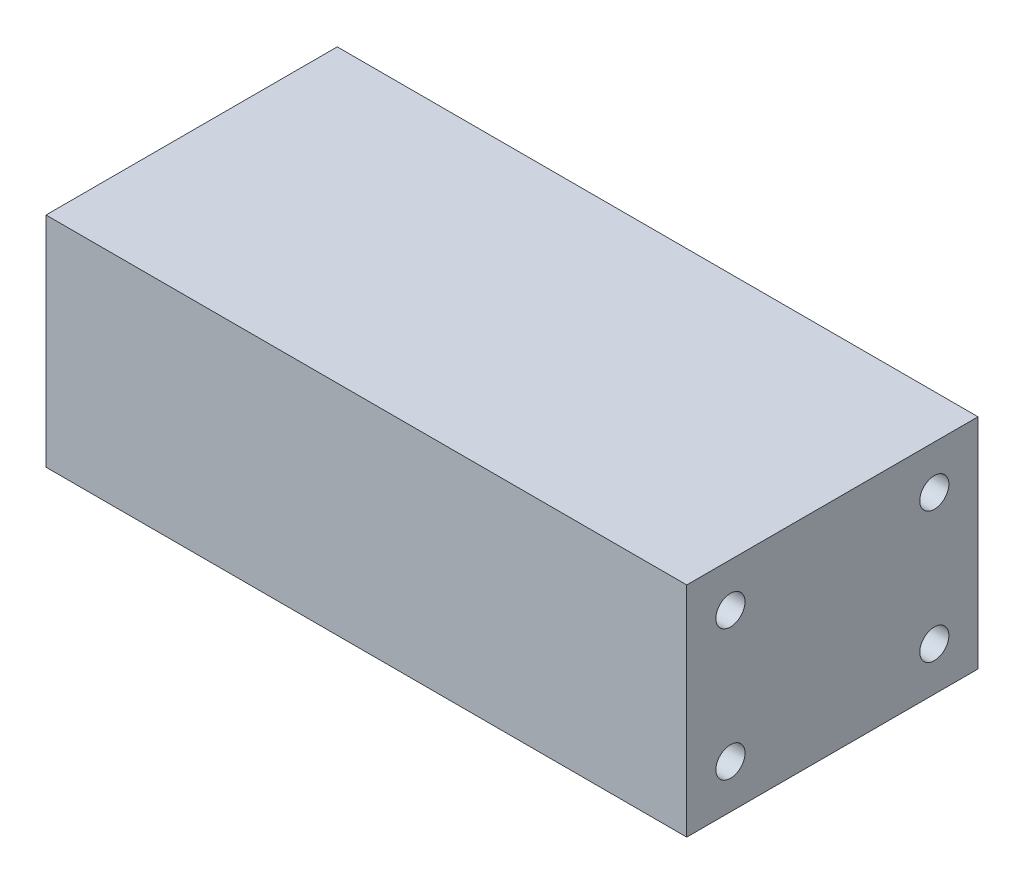
SolidWorks part; units mm, degrees
ref_plane "Front Plane" through (0, 0, 0) normal (0, 0, 1) x (1, 0, 0)
ref_plane "Top Plane" through (0, 0, 0) normal (0, 1, 0) x (1, 0, 0)
ref_plane "Right Plane" through (0, 0, 0) normal (1, 0, 0) x (0, 0, -1)
sketch "Sketch1" plane through (0, 0, 0) normal (1, 0, 0) x (0, 0, -1)
  line L0 (10, 0) -> (10, 15)
  line L1 (0, 0) -> (20, 0)
  line L2 (0, 0) -> (0, 15)
  line L3 (0, 15) -> (20, 15)
  line L4 (20, 0) -> (20, 15)
  line L5 (0, 7.5) -> (20, 7.5)
  circle A0 centre (3, 12) radius 1
  circle A1 centre (17, 12) radius 1
  circle A2 centre (17, 3) radius 1
  circle A3 centre (3, 3) radius 1
  dimension "D3" = 2
  dimension "D4" = 3
  dimension "D5" = 3
  dimension "D1" = 20
  dimension "D2" = 15
extrude "Boss-Extrude1" add sketch "Sketch1" against normal blind 44 contours L2 L5 L0 L3 A0 | A0 | L0 L5 L4 L3 A1 | A1 | L5 L0 L1 L4 A2 | A2 | L5 L2 L1 L0 A3 | A3 region at (0, 3.7828, -5.0874) region at (0, 3.7828, -14.9126) region at (0, 11.2172, -5.0874) region at (0, 11.2172, -14.9126) region at (0, 12, -3) region at (0, 12, -17) region at (0, 3, -17) region at (0, 3, -3)
extrude "Cut-Extrude1" cut sketch "Sketch1<3>" against normal blind 5 contours A0 | A1 | A2 | A3 region at (0, 12, -3) region at (0, 12, -17) region at (0, 3, -17)
sketch "Sketch1<3>" plane through (0, 0, 0) normal (1, 0, 0) x (0, 0, -1) same geometry as "Sketch1"
ref_plane "Plane1" through (-44, 0, 0) normal (-1, 0, 0) x (0, 0, 1)
sketch "Sketch2" plane through (-44, 0, 0) normal (-1, 0, 0) x (0, 0, 1)
  line L0 (-10, 15) -> (-10, 0)
  line L1 (0, 15) -> (-20, 15) construction
  line L2 (55, 0) -> (-55, 0) construction
  line L3 (-20, 7.5) -> (0, 7.5)
  line L4 (-20, 0) -> (-20, 15) construction
  line L5 (0, -55) -> (0, 55) construction
  circle A0 centre (-17, 12) radius 1
  circle A1 centre (-3, 12) radius 1
  circle A2 centre (-3, 3) radius 1
  circle A3 centre (-17, 3) radius 1
  dimension "D1" = 2
  dimension "D2" = 3
  dimension "D3" = 3
extrude "Cut-Extrude2" cut sketch "Sketch2" against normal blind 5 contours A0 | A1 | A2 | A3 region at (-44, 12, -17) region at (-44, 12, -3) region at (-44, 3, -3) region at (-44, 3, -17)
